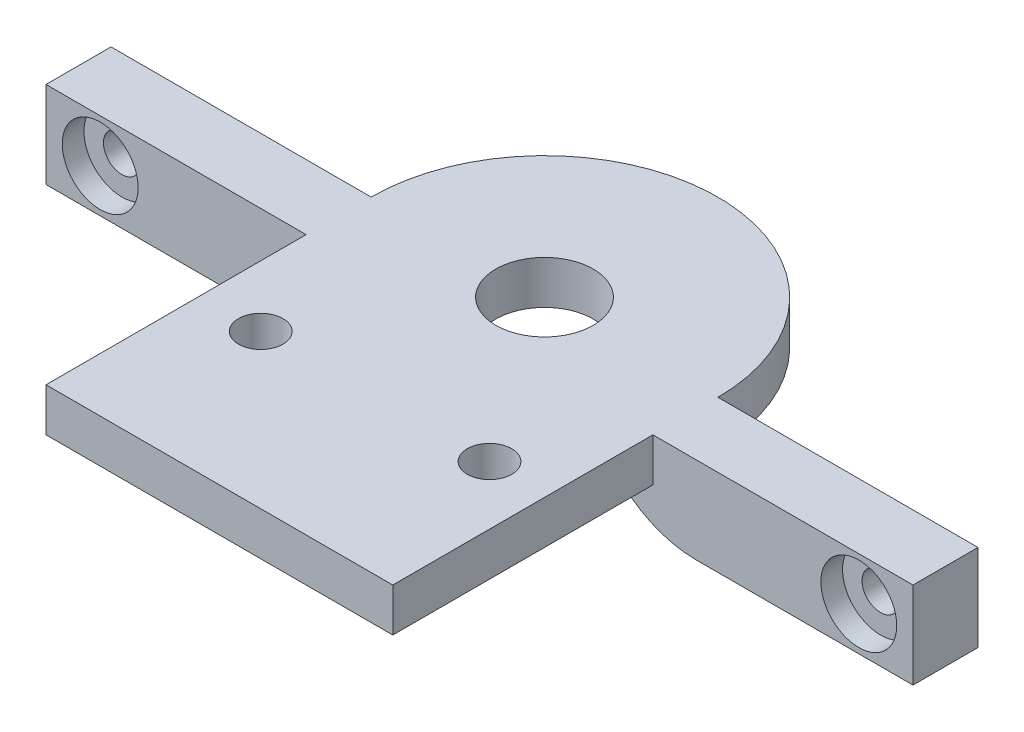
SolidWorks part; units mm, degrees
ref_plane "Front Plane" through (0, 0, 0) normal (0, 0, 1) x (1, 0, 0)
ref_plane "Top Plane" through (0, 0, 0) normal (0, 1, 0) x (1, 0, 0)
ref_plane "Right Plane" through (0, 0, 0) normal (1, 0, 0) x (0, 0, -1)
sketch "Sketch1" plane through (0, 0, 0) normal (0, 1, 0) x (1, 0, 0)
  line L13 (-16, 0) -> (-16, -30)
  line L16 (-16, -30) -> (16, -30)
  line L19 (16, 0) -> (16, -30)
  circle A0 centre (0, 0) radius 4.5
  arc A1 (-16, 0) -> (16, 0) centre (0, 0) cw
  point P12 (0, -30)
  dimension "D1" = 9
  dimension "D2" = 16
  dimension "D3" = 30
extrude "Boss-Extrude1" add sketch "Sketch1" along normal blind 4
sketch "Sketch2" plane through (0, 4, 0) normal (0, 1, 0) x (1, 0, 0)
  line L0 (0, 20.52) -> (0, -35.5828) construction
  line L1 (16, 0) -> (40, 0)
  line L2 (16, 0) -> (16, -6)
  line L3 (16, -6) -> (40, -6)
  line L4 (40, 0) -> (40, -6)
  line L5 (-16, -6) -> (-40, -6)
  line L6 (-40, 0) -> (-40, -6)
  line L7 (-16, 0) -> (-40, 0)
  line L8 (-16, 0) -> (-16, -6)
  dimension "D1" = 40
  dimension "D2" = 6
extrude "Boss-Extrude2" add sketch "Sketch2" against normal blind 8
hole_wizard "CBORE for M3 Hexagon head bolts-Full thread-grades AB1" positions "3DSketch1" profile "Sketch3" counterbore size "M3" standard "GB" end condition through all
sketch3d "3DSketch1"
  line L0 (-40, -4, 6) -> (-40, 4, 6) construction
  line L1 (40, -4, 6) -> (40, 4, 6) construction
  point P0 (-35, 0, 6)
  point P2 (35, 0, 6)
  point P5 (0, 0, 0)
  point P8 (-40, 0, 6)
  point P9 (0, 0, 0)
  point P12 (40, 0, 6)
  point P13 (0, 0, 0)
  point P14 (0, 0, 0)
  dimension "D1" = 5
  dimension "D2" = 5
sketch "Sketch3" plane through (-35, 0, 6) normal (1, 0, 0) x (0, -1, 0)
  line L0 (0, 0) -> (0, 22)
  line L1 (0, 22) -> (1.7, 22)
  line L3 (1.7, 22) -> (1.7, 2)
  line L4 (1.7, 2) -> (3.5, 2)
  line L5 (3.5, 2) -> (3.5, 0)
  line L7 (3.5, 0) -> (0, 0)
  line L11 (0, -6.35) -> (0, 107.95) construction
  dimension "Thru Hole Dia." = 3.4
  dimension "Thru Hole Depth" = 22
  dimension "C'Bore Dia." = 7
  dimension "C'Bore Depth" = 2
fillet "Fillet1" radius 10 2 edges at (16, 0, 3) (-16, 0, 3)
fillet "Fillet2" radius 10 2 edges at (16, -4, 3) (-16, -4, 3)
sketch "Sketch4" plane through (0, 4, 0) normal (0, 1, 0) x (1, 0, 0)
  circle A0 centre (10.5947, -15.6694) radius 1.9812 construction
  circle A1 centre (-10.3597, -15.8257) radius 1.9812 construction
  circle A2 centre (10.5947, -15.6694) radius 1.9812
  circle A3 centre (-10.3597, -15.8257) radius 1.9812
  circle A4 centre (-10.3597, -15.8257) radius 2.05
  circle A5 centre (10.5947, -15.6694) radius 2.05
  point P0 (0, -21.1501)
  dimension "D1" = 4.1
  dimension "D2" = 4.1
extrude "Cut-Extrude2" cut sketch "Sketch4" against normal through all contours A4 A3 | A3 | A2 | A5 A2 region at (10.5947, 4, 15.6694) region at (-10.3597, 4, 15.8257) region at (-12.3517, 4, 15.8257) region at (8.6027, 4, 15.6694)
